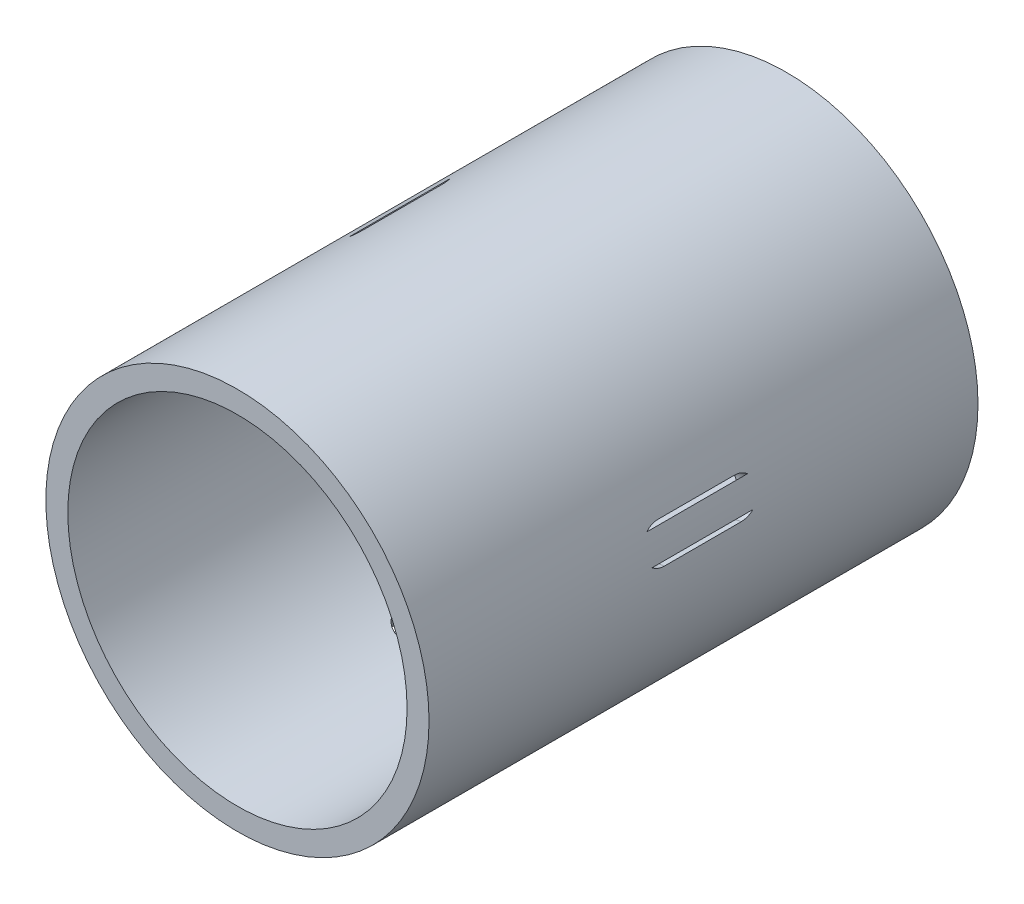
SolidWorks part; units mm, degrees
ref_plane "Plan de face" through (0, 0, 0) normal (0, 0, 1) x (1, 0, 0)
ref_plane "Plan de dessus" through (0, 0, 0) normal (0, 1, 0) x (1, 0, 0)
ref_plane "Plan de droite" through (0, 0, 0) normal (1, 0, 0) x (0, 0, -1)
sketch "Esquisse1" plane through (0, 0, 0) normal (0, 0, 1) x (1, 0, 0)
  circle A1 centre (0, 0) radius 15.45
  arc A3 (4.3471, 16.9515) -> (-7.3611, -15.8765) centre (0, 0) ccw construction
  circle A5 centre (0, 0) radius 17.45
  dimension "D1" = 2
  dimension "D2" = 0.05
extrude "Boss.-Extru.1" add sketch "Esquisse1" against normal blind 50
ref_plane "Plan1" through (-5.8451, -16.3889, 0) normal (-0.3359, -0.9419, 0) x (-0.9419, 0.3359, 0)
sketch "Esquisse2" plane through (-5.8451, -16.3889, 0) normal (-0.3359, -0.9419, 0) x (-0.9419, 0.3359, 0)
  line L0 (0, 28.5) -> (0, 21.5) construction
  line L1 (1.7, 28.5) -> (1.7, 21.5)
  line L2 (-1.7, 28.5) -> (-1.7, 21.5)
  line L3 (0, 28.5) -> (0, 21.5) construction
  line L4 (0, 50) -> (0, 0) construction
  line L5 (17.4, 50) -> (-17.4, 50) construction
  line L6 (-17.4, 0) -> (17.4, 0) construction
  arc A0 (1.7, 28.5) -> (-1.7, 28.5) centre (0, 28.5) ccw
  arc A1 (-1.7, 21.5) -> (1.7, 21.5) centre (0, 21.5) ccw
  point P3 (0, 25)
  dimension "D1" = 3.4
extrude "Enlèv. mat.-Extru.1" cut sketch "Esquisse2" against normal up to next
ref_plane "Plan2" through (17.1157, 3.1324, 0) normal (0.9837, 0.18, 0) x (0, 0, 1)
sketch "Esquisse4" plane through (17.1157, 3.1324, 0) normal (0.9837, 0.18, 0) x (0, 0, 1)
  line L2 (-28.5, 0) -> (-21.5, 0) construction
  line L3 (-28.5, 1.71) -> (-21.5, 1.71)
  line L4 (-28.5, -1.71) -> (-21.5, -1.71)
  line L5 (-28.5, 14.1467) -> (-21.5, 14.1467) construction
  line L6 (0, 0) -> (-50, 0) construction
  line L7 (-50, 17.4) -> (-50, -17.4) construction
  line L8 (0, -17.4) -> (0, 17.4) construction
  arc A0 (-28.5, 1.71) -> (-28.5, -1.71) centre (-28.5, 0) ccw
  arc A1 (-21.5, -1.71) -> (-21.5, 1.71) centre (-21.5, 0) ccw
  point P2 (-25, 0)
  dimension "D1" = 3.42
extrude "Enlèv. mat.-Extru.2" cut sketch "Esquisse4" against normal up to next
ref_plane "Plan3" through (-11.2706, 13.2564, 0) normal (-0.6477, 0.7619, 0) x (0, 0, 1)
sketch "Esquisse5" plane through (-11.2706, 13.2564, 0) normal (-0.6477, 0.7619, 0) x (0, 0, 1)
  line L0 (0, 0) -> (-50, 0) construction
  line L3 (-50, 17.4) -> (-50, -17.4) construction
  line L4 (-28.5, 0) -> (-21.5, 0) construction
  line L5 (-28.5, 1.72) -> (-21.5, 1.72)
  line L6 (-28.5, -1.72) -> (-21.5, -1.72)
  line L7 (-28.5, -15.8467) -> (-21.5, -15.8467) construction
  arc A0 (-28.5, 1.72) -> (-28.5, -1.72) centre (-28.5, 0) ccw
  arc A1 (-21.5, -1.72) -> (-21.5, 1.72) centre (-21.5, 0) ccw
  point P7 (-25, 0)
  dimension "D1" = 3.44
extrude "Enlèv. mat.-Extru.3" cut sketch "Esquisse5" against normal up to surface (2.046 mm away) up to face at (15.1503, 2.7727, -25)
ref_axis "Axe1" through (-4.7557, -13.3343, -21.5) along (-0.3359, -0.9419, 0)
ref_axis "Axe2" through (14.3972, 2.6349, -21.5) along (0.9837, 0.18, 0)
ref_axis "Axe3" through (-9.7849, 11.5089, -21.5) along (-0.6477, 0.7619, 0)
